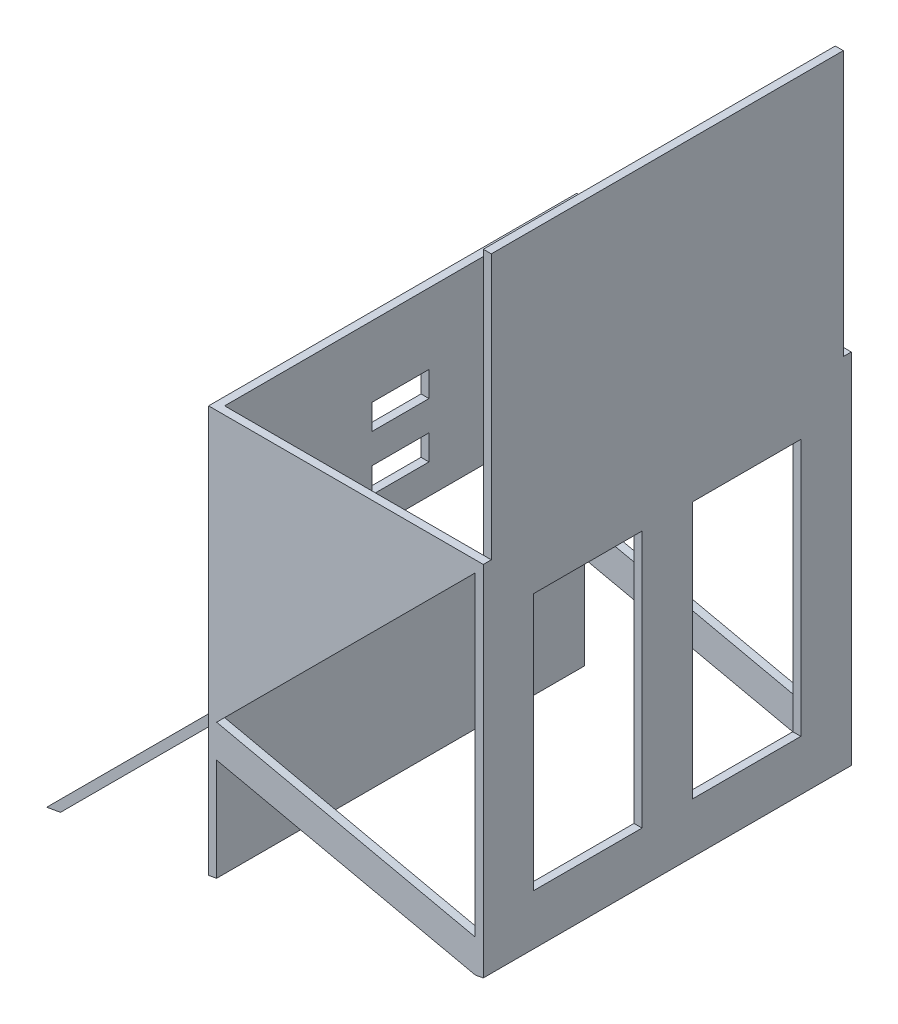
SolidWorks part; units mm, degrees
material "Teak"
ref_plane "Front Plane" through (0, 0, 0) normal (0, 0, 1) x (1, 0, 0)
ref_plane "Top Plane" through (0, 0, 0) normal (0, 1, 0) x (1, 0, 0)
ref_plane "Right Plane" through (0, 0, 0) normal (1, 0, 0) x (0, 0, -1)
sketch "Sketch1" plane through (0, 0, 0) normal (0, 1, 0) x (1, 0, 0)
  line L1 (-102.5, 139.5) -> (102.5, 139.5)
  line L2 (-102.5, 139.5) -> (-102.5, -139.5)
  line L3 (-102.5, -139.5) -> (102.5, -139.5)
  line L4 (102.5, 139.5) -> (102.5, -139.5)
  line L5 (-102.5, 139.5) -> (102.5, -139.5) construction
  line L6 (-102.5, -139.5) -> (102.5, 139.5) construction
  line L7 (-108.85, 145.85) -> (108.85, 145.85)
  line L8 (-108.85, 145.85) -> (-108.85, -145.85)
  line L9 (-108.85, -145.85) -> (108.85, -145.85)
  line L10 (108.85, 145.85) -> (108.85, -145.85)
  line L11 (-108.85, 145.85) -> (108.85, -145.85) construction
  line L12 (-108.85, -145.85) -> (108.85, 145.85) construction
  point P0 (0, 0)
  point P5 (0, 0)
  dimension "D1" = 279
  dimension "D2" = 205
  dimension "D3" = 6.35
  dimension "D4" = 6.35
sketch3d "3DSketch1"
  line L0 (102.5, 150, 0) -> (102.5, 0, 0) construction
  line L1 (102.5, 0, 0) -> (0, 0, 0) construction
  line L2 (102.5, 0, 102.7399) -> (102.5, 0, -102.7399) construction
  line L3 (102.5, 0, 0) -> (102.5, -285, 0) construction
  line L4 (102.5, -285, -65.8407) -> (102.5, -285, 65.8407) construction
  line L5 (102.5, 0, -139.5) -> (102.5, 0, 139.5) construction
  dimension "D1" = 150
  dimension "D2" = 285
ref_plane "Base Plane" through (51.25, -51.25, 0) normal (-0.7071, 0.7071, 0) x (0, 0, -1)
ref_plane "Launch Plane" through (51.8286, -293.9347, 0) normal (-0.1736, 0.9848, 0) x (0, 0, 1)
ref_plane "Box Bottom Plane (Approx)" through (0, -500, 0) normal (0, 1, 0) x (1, 0, 0)
extrude "Boss-Extrude1" add sketch "Sketch1" against normal up to surface (285 mm away) up to plane "Launch Plane"
sketch "Sketch7" plane through (0, 0, 0) normal (0, 0, 1) x (1, 0, 0)
  line L0 (102.5, 0) -> (-243.5111, -346.0111)
  line L1 (-243.5111, -346.0111) -> (-232.6084, -344.0887)
  line L2 (131.1629, 28.6629) -> (-28.6629, -131.1629) construction
  line L3 (119.735, 0) -> (-119.735, 0) construction
  line L4 (102.5, 0) -> (102.5, -8.9803)
  line L5 (102.5, -8.9803) -> (-232.6084, -344.0887)
  line L6 (123.1531, -281.3583) -> (-19.4958, -306.5112) construction
  dimension "D1" = 6.35
extrude "Boss-Extrude4" add sketch "Sketch7" against normal up to surface and the other way up to surface up to face at (0, -151.5368, -139.5) other way up to face at (0, -151.5368, 139.5)
sketch "Sketch8" plane through (0, 0, 0) normal (0, 1, 0) x (1, 0, 0)
  line L0 (108.85, 145.85) -> (108.85, -145.85) construction
  line L1 (102.5, 139.5) -> (108.85, 139.5)
  line L2 (102.5, 139.5) -> (102.5, -139.5)
  line L3 (102.5, -139.5) -> (108.85, -139.5)
  line L4 (108.85, 139.5) -> (108.85, -139.5)
  line L5 (-102.5, -139.5) -> (102.5, -139.5) construction
extrude "Boss-Extrude5" add sketch "Sketch8" along normal blind 210
sketch "Sketch4" plane through (0, 0, 0) normal (0, 0, 1) x (1, 0, 0)
  line L0 (-108.85, -211.35) -> (-102.5, -205)
  line L1 (-108.85, -143) -> (-102.5, -143)
  line L2 (-102.5, -205) -> (-102.5, 0) construction
  line L3 (-108.85, -211.35) -> (-108.85, -143)
  line L4 (-108.85, -322.2667) -> (-108.85, 0) construction
  line L5 (-102.5, -143) -> (-102.5, -205)
  line L7 (131.1629, 28.6629) -> (-28.6629, -131.1629) construction
  dimension "D2" = 62
extrude "Cut-Extrude1" cut sketch "Sketch4" against normal up to surface and the other way up to surface up to face at (-34.1667, -68.3333, -139.5) other way up to face at (-34.1667, -68.3333, 139.5)
sketch "Sketch6" plane through (0, 0, 0) normal (0, 0, 1) x (1, 0, 0)
  line L8 (-108.85, -99.5) -> (-102.5, -99.5)
  line L9 (-108.85, -99.5) -> (-108.85, -119.5)
  line L10 (-108.85, -119.5) -> (-102.5, -119.5)
  line L11 (-102.5, -99.5) -> (-102.5, -119.5)
  line L12 (-102.5, -143) -> (-102.5, -205) construction
  line L13 (-108.85, -56) -> (-102.5, -56)
  line L14 (-108.85, -56) -> (-108.85, -76)
  line L15 (-108.85, -76) -> (-102.5, -76)
  line L16 (-102.5, -56) -> (-102.5, -76)
  line L17 (-108.85, -143) -> (-102.5, -143) construction
  line L18 (-108.85, -211.35) -> (-108.85, -143) construction
  point P5 (-105.675, -99.5)
  dimension "D1" = 20
  dimension "D2" = 43.5
  dimension "D4" = 20
  dimension "D5" = 43.5
extrude "Cut-Extrude2" cut sketch "Sketch6" against normal mid plane 45
sketch "Sketch9" plane through (0, 0, 0) normal (0, 0, 1) x (1, 0, 0)
  line L0 (-102.5, -321.147) -> (-102.5, -239.9854)
  line L1 (108.85, -283.8803) -> (-108.85, -322.2667) construction
  line L2 (-102.5, -239.9854) -> (102.5, -285)
  line L3 (102.5, -285) -> (-102.5, -321.147)
  line L4 (-102.5, -213.9803) -> (102.5, -8.9803)
  line L5 (102.5, -8.9803) -> (102.5, -258.9949)
  line L6 (102.5, -258.9949) -> (-102.5, -213.9803)
  line L8 (-108.85, -322.2667) -> (-108.85, 0) construction
  line L10 (131.1629, 28.6629) -> (-28.6629, -131.1629) construction
  line L11 (108.85, -283.8803) -> (108.85, 0) construction
  point P15 (0, 0)
  point P16 (102.5, -259.0484)
  dimension "D1" = 6.35
  dimension "D2" = 6.35
  dimension "D3" = 6.35
  dimension "D4" = 25.4
extrude "Cut-Extrude3" cut sketch "Sketch9" against normal through all both and the other way through all
sketch "Sketch10" plane through (108.85, 0, 0) normal (1, 0, 0) x (0, 0, -1)
  line L0 (145.85, -283.8803) -> (-145.85, -283.8803) construction
  line L3 (-20, -40) -> (-105.85, -40)
  line L6 (-20, -40) -> (20, -40) construction
  line L7 (0, 0) -> (0, -40) construction
  line L8 (-20, -40) -> (-20, -243.8803)
  line L9 (-20, -243.8803) -> (-105.85, -243.8803)
  line L10 (-105.85, -40) -> (-105.85, -243.8803)
  line L11 (20, -40) -> (105.85, -40)
  line L12 (20, -40) -> (20, -243.8803)
  line L13 (20, -243.8803) -> (105.85, -243.8803)
  line L14 (105.85, -40) -> (105.85, -243.8803)
  line L15 (-145.85, -283.8803) -> (-145.85, 0) construction
  dimension "D1" = 40
  dimension "D2" = 40
  dimension "D3" = 40
  dimension "D4" = 40
extrude "Cut-Extrude4" cut sketch "Sketch10" against normal up to next
equation "\"Frisbee Width\"=274"
equation "\"D1@Sketch1\"=\"Frisbee Width\"+5"
equation "\"Wall Thickness\"= 6.35"
equation "\"D3@Sketch1\"=\"Wall Thickness\""
equation "\"D4@Sketch1\"=\"Wall Thickness\""
equation "\"D2@Sketch4\"=85-23"
equation "\"D1@Sketch7\"=\"Wall Thickness\""
equation "\"D1@Sketch9\"=\"Wall Thickness\""
equation "\"D2@Sketch9\"=\"Wall Thickness\""
equation "\"D3@Sketch9\"=\"Wall Thickness\""
